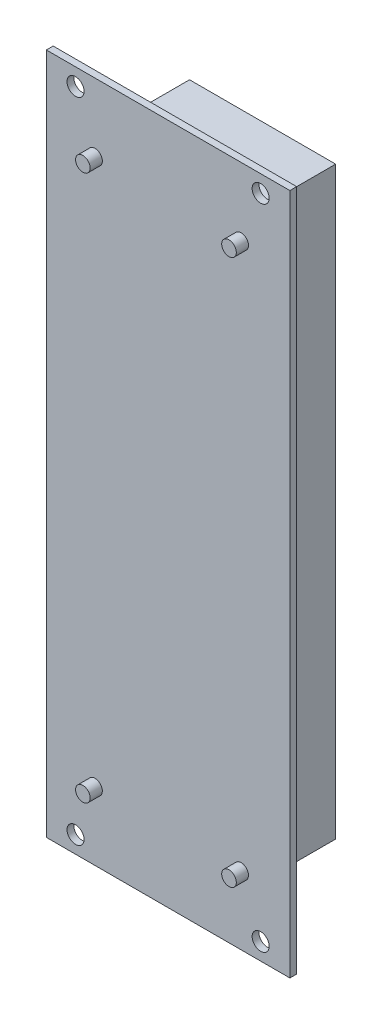
SolidWorks part; units mm, degrees
ref_plane "Front Plane" through (0, 0, 0) normal (0, 0, 1) x (1, 0, 0)
ref_plane "Top Plane" through (0, 0, 0) normal (0, 1, 0) x (1, 0, 0)
ref_plane "Right Plane" through (0, 0, 0) normal (1, 0, 0) x (0, 0, -1)
sketch "Sketch1" plane through (0, 0, 0) normal (0, 0, 1) x (1, 0, 0)
  line L1 (-25, -70) -> (25, -70)
  line L2 (-25, -70) -> (-25, 70)
  line L3 (-25, 70) -> (25, 70)
  line L4 (25, -70) -> (25, 70)
  line L5 (-25, -70) -> (25, 70) construction
  line L6 (-25, 70) -> (25, -70) construction
  point P0 (0, 0)
  dimension "D1" = 140
  dimension "D2" = 50
extrude "Boss-Extrude1" add sketch "Sketch1" along normal mid plane 1.4
sketch "Sketch3" plane through (0, 0, -0.7) normal (0, 0, -1) x (-1, 0, 0)
  line L12 (-15, 60) -> (-15, -60)
  line L13 (-15, -60) -> (15, -60)
  line L14 (15, -60) -> (15, 60)
  line L15 (15, 60) -> (-15, 60)
  line L16 (-15, 60) -> (-15, -60)
  line L17 (-15, -60) -> (15, -60)
  line L18 (15, -60) -> (15, 60)
  line L19 (15, 60) -> (-15, 60)
  dimension "D1" = 10
extrude "Boss-Extrude2" add sketch "Sketch3" along normal blind 18
sketch "Sketch4" plane through (0, 0, -0.7) normal (0, 0, -1) x (-1, 0, 0)
  line L1 (-19, -66.5) -> (19, -66.5) construction
  line L2 (-19, -66.5) -> (-19, 66.5) construction
  line L3 (-19, 66.5) -> (19, 66.5) construction
  line L4 (19, -66.5) -> (19, 66.5) construction
  line L5 (-19, -66.5) -> (19, 66.5) construction
  line L6 (-19, 66.5) -> (19, -66.5) construction
  circle A0 centre (-19, 66.5) radius 1.75
  circle A1 centre (19, 66.5) radius 1.75
  circle A2 centre (-19, -66.5) radius 1.75
  circle A3 centre (19, -66.5) radius 1.75
  point P0 (0, 0)
  dimension "D3" = 3.5
  dimension "D1" = 38
  dimension "D2" = 133
extrude "Cut-Extrude1" cut sketch "Sketch4" against normal up to surface (1.4 mm away) up to face at (0, 0, 0.7)
sketch "Sketch5" plane through (0, 0, 0.7) normal (0, 0, 1) x (1, 0, 0)
  line L0 (25, 70) -> (-25, 70) construction
  line L1 (-15, -56) -> (15, -56) construction
  line L2 (-15, -56) -> (-15, 56) construction
  line L3 (-15, 56) -> (15, 56) construction
  line L4 (15, -56) -> (15, 56) construction
  line L5 (-15, -56) -> (15, 56) construction
  line L6 (-15, 56) -> (15, -56) construction
  line L7 (25, -70) -> (25, 70) construction
  circle A0 centre (15, 56) radius 1.5
  circle A1 centre (-15, 56) radius 1.5
  circle A2 centre (-15, -56) radius 1.5
  circle A3 centre (15, -56) radius 1.5
  point P0 (0, 0)
  dimension "D3" = 3
  dimension "D1" = 14
  dimension "D2" = 10
extrude "Boss-Extrude3" add sketch "Sketch5" along normal blind 2.5
